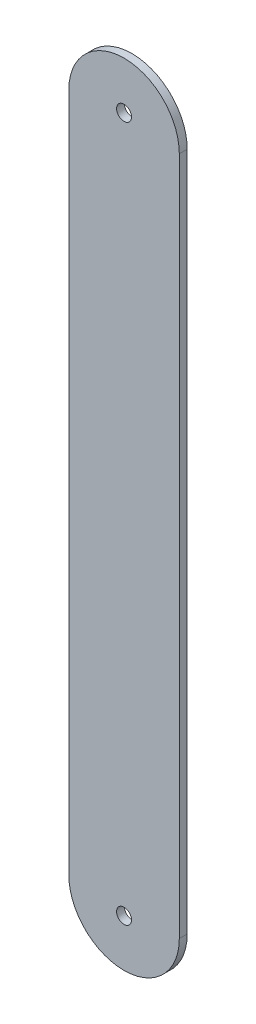
SolidWorks part; units mm, degrees
material "Thornel Mat VMA"
ref_plane "Front Plane" through (0, 0, 0) normal (0, 0, 1) x (1, 0, 0)
ref_plane "Top Plane" through (0, 0, 0) normal (0, 1, 0) x (1, 0, 0)
ref_plane "Right Plane" through (0, 0, 0) normal (1, 0, 0) x (0, 0, -1)
sketch "Sketch1" plane through (0, 0, 0) normal (0, 0, 1) x (1, 0, 0)
  line L0 (0, 68.3375) -> (0, -68.3375) construction
  line L1 (-11.1125, 68.3375) -> (11.1125, 68.3375)
  line L2 (-11.1125, 68.3375) -> (-11.1125, -68.3375)
  line L3 (-11.1125, -68.3375) -> (11.1125, -68.3375)
  line L4 (11.1125, 68.3375) -> (11.1125, -68.3375)
  arc A0 (-11.1125, 68.3375) -> (11.1125, 68.3375) centre (0, 68.3375) cw
  arc A1 (-11.1125, -68.3375) -> (11.1125, -68.3375) centre (0, -68.3375) ccw
  circle A2 centre (0, -69.925) radius 1.5
  circle A3 centre (0, 69.925) radius 1.5
  point P10 (0, 79.45)
  point P11 (0, -79.45)
  point P14 (0, 0)
  dimension "D2" = 139.85
  dimension "D5" = 3
  dimension "D6" = 3
  dimension "D1" = 22.225
  dimension "D3" = 9.525
  dimension "D4" = 9.525
extrude "Boss-Extrude1" add sketch "Sketch1" along normal blind 1.5875 contours A0 L1 A3 | L1 L0 L3 L4 | L0 L1 L2 L3 | L3 A1 A2 region at (5.5563, 0, 0) region at (-5.5563, 0, 0) region at (0, 73.1721, 0) region at (0, -73.1721, 0)
